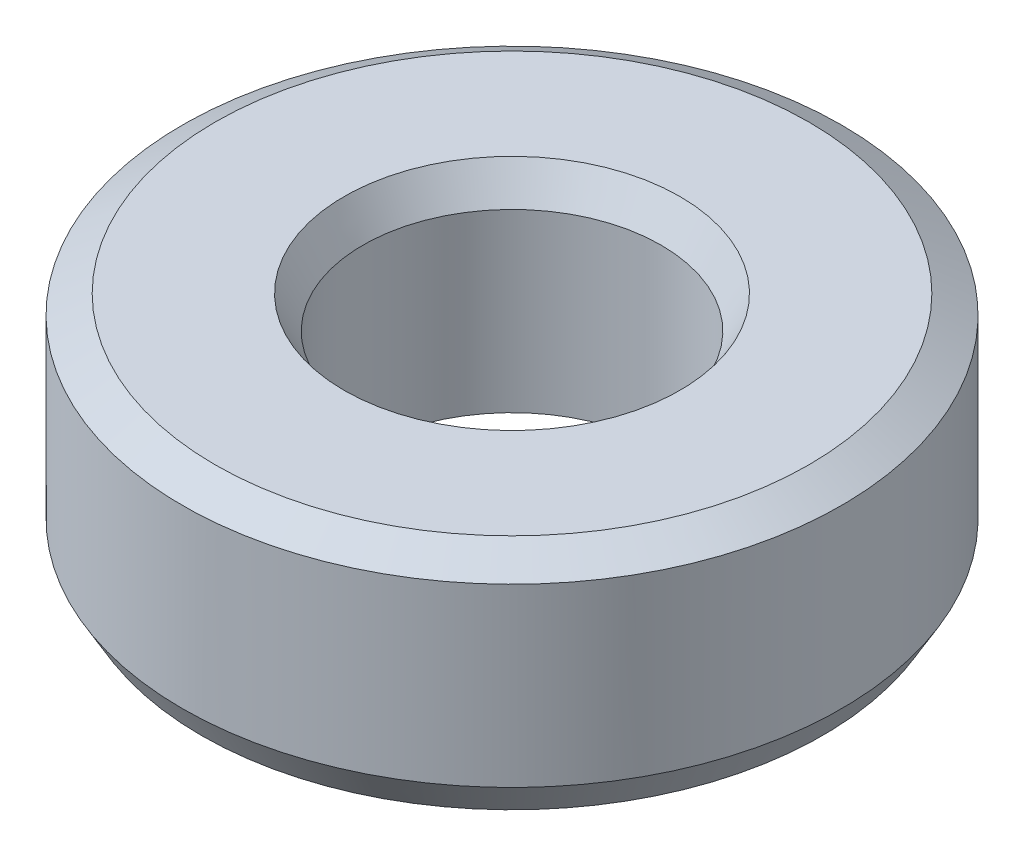
SolidWorks part; units mm, degrees
ref_plane "Front Plane" through (0, 0, 0) normal (0, 0, 1) x (1, 0, 0)
ref_plane "Top Plane" through (0, 0, 0) normal (0, 1, 0) x (1, 0, 0)
ref_plane "Right Plane" through (0, 0, 0) normal (1, 0, 0) x (0, 0, -1)
sketch "Sketch1" plane through (0, 0, 0) normal (0, 1, 0) x (1, 0, 0)
  circle A0 centre (0, 0) radius 45
  dimension "SLEEVE_OD" = 90
extrude "Boss-Extrude1" add sketch "Sketch1" along normal blind 31.0686
sketch "Sketch2" plane through (0, 0, 0) normal (0, 1, 0) x (1, 0, 0)
  circle A0 centre (0, 0) radius 20.3565
  dimension "BORE_D" = 40.7131
extrude "Cut-Extrude1" cut sketch "Sketch2" along normal through all
chamfer "Chamfer1" distance 2.5746 angle 60 4 edges at (0, 31.0686, 20.3565) (0, 0, 20.3565) (0, 0, 45) (0, 31.0686, 45) first distance on face at (0, 31.0686, 20.3565) first distance on face at (0, 0, 20.3565) first distance on face at (0, 31.0686, 45)
